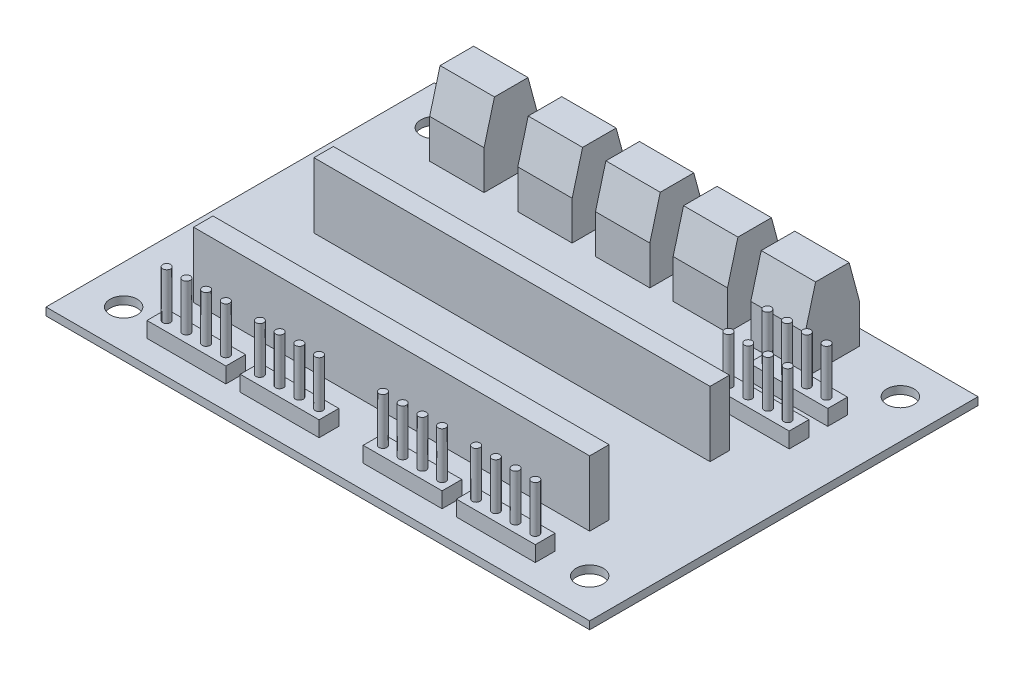
SolidWorks part; units mm, degrees
material "ABS"
ref_plane "Спереди" through (0, 0, 0) normal (0, 0, 1) x (1, 0, 0)
ref_plane "Сверху" through (0, 0, 0) normal (0, 1, 0) x (1, 0, 0)
ref_plane "Справа" through (0, 0, 0) normal (1, 0, 0) x (0, 0, -1)
sketch "Эскиз2" plane through (0, 0, 0) normal (0, 1, 0) x (1, 0, 0)
  line L0 (0, 25) -> (113.3637, 25) construction
  line L1 (0, 0) -> (70, 0)
  line L2 (0, 0) -> (0, 50)
  line L3 (0, 50) -> (70, 50)
  line L4 (70, 0) -> (70, 50)
  line L5 (35, 50) -> (35, -7.1391) construction
  circle A0 centre (5, 45) radius 1.75
  circle A1 centre (65, 45) radius 1.75
  circle A2 centre (65, 5) radius 1.75
  circle A3 centre (5, 5) radius 1.75
  dimension "D3" = 3.5
  dimension "D1" = 70
  dimension "D2" = 50
  dimension "D4" = 5
  dimension "D5" = 5
extrude "Бобышка-Вытянуть1" add sketch "Эскиз2" along normal blind 1
sketch "Эскиз3" plane through (0, 1, 0) normal (0, 1, 0) x (1, 0, 0)
  line L0 (0, 0) -> (70, 0) construction
  line L1 (9, 12.5) -> (60, 12.5)
  line L2 (9, 12.5) -> (9, 10)
  line L3 (9, 10) -> (60, 10)
  line L4 (60, 12.5) -> (60, 10)
  line L9 (70, 0) -> (70, 50) construction
  line L10 (60, 12.5) -> (60, 19) construction
  line L11 (60, 19) -> (7.0253, 19) construction
  line L12 (9, 28) -> (60, 28)
  line L13 (60, 25.5) -> (60, 28)
  line L14 (9, 25.5) -> (60, 25.5)
  line L15 (9, 25.5) -> (9, 28)
  dimension "D1" = 2.5
  dimension "D2" = 51
  dimension "D6" = 10
  dimension "D7" = 10
extrude "Бобышка-Вытянуть2" add sketch "Эскиз3" along normal blind 8.4
sketch "Эскиз4" plane through (0, 1, 0) normal (0, 1, 0) x (1, 0, 0)
  line L0 (70, 0) -> (70, 50) construction
  line L1 (60, 5.54) -> (49.84, 5.54)
  line L2 (60, 5.54) -> (60, 3)
  line L3 (60, 3) -> (49.84, 3)
  line L4 (49.84, 5.54) -> (49.84, 3)
  line L5 (0, 0) -> (70, 0) construction
  line L6 (48, 5.54) -> (48, 3)
  line L7 (35, 0) -> (35, 38.4524) construction
  line L8 (48, 5.54) -> (37.84, 5.54)
  line L9 (37.84, 5.54) -> (37.84, 3)
  line L10 (48, 3) -> (37.84, 3)
  line L11 (10, 3) -> (20.16, 3)
  line L12 (20.16, 5.54) -> (20.16, 3)
  line L13 (10, 5.54) -> (20.16, 5.54)
  line L14 (10, 5.54) -> (10, 3)
  line L15 (22, 5.54) -> (32.16, 5.54)
  line L16 (32.16, 5.54) -> (32.16, 3)
  line L17 (22, 3) -> (32.16, 3)
  line L18 (22, 5.54) -> (22, 3)
  line L19 (53.4823, 37.0132) -> (63.6423, 37.0132)
  line L20 (53.4823, 37.0132) -> (53.4823, 39.5532)
  line L21 (53.4823, 39.5532) -> (63.6423, 39.5532)
  line L22 (63.6423, 37.0132) -> (63.6423, 39.5532)
  line L23 (53.5146, 32.0132) -> (63.6746, 32.0132)
  line L24 (53.5146, 32.0132) -> (53.5146, 34.5532)
  line L25 (53.5146, 34.5532) -> (63.6746, 34.5532)
  line L26 (63.6746, 32.0132) -> (63.6746, 34.5532)
  dimension "D1" = 2.54
  dimension "D2" = 10.16
  dimension "D3" = 10
  dimension "D4" = 3
  dimension "D6" = 5
  dimension "D5" = 2
extrude "Бобышка-Вытянуть3" add sketch "Эскиз4" along normal blind 2
sketch "Эскиз5" plane through (0, 3, 0) normal (0, 1, 0) x (1, 0, 0)
  line L0 (60, 3) -> (60, 5.54) construction
  line L1 (49.84, 3) -> (60, 3) construction
  line L2 (35, 0) -> (35, 20.127) construction
  line L3 (0, 0) -> (70, 0) construction
  circle A0 centre (58.73, 4.27) radius 0.5
  circle A1 centre (56.19, 4.27) radius 0.5
  circle A2 centre (53.65, 4.27) radius 0.5
  circle A3 centre (51.11, 4.27) radius 0.5
  circle A4 centre (46.73, 4.27) radius 0.5
  circle A5 centre (44.19, 4.27) radius 0.5
  circle A6 centre (41.65, 4.27) radius 0.5
  circle A7 centre (39.11, 4.27) radius 0.5
  circle A8 centre (25.81, 4.27) radius 0.5
  circle A9 centre (11.27, 4.27) radius 0.5
  circle A10 centre (13.81, 4.27) radius 0.5
  circle A11 centre (16.35, 4.27) radius 0.5
  circle A12 centre (18.89, 4.27) radius 0.5
  circle A13 centre (23.27, 4.27) radius 0.5
  circle A14 centre (28.35, 4.27) radius 0.5
  circle A15 centre (30.89, 4.27) radius 0.5
  circle A16 centre (54.671, 33.2084) radius 0.5
  circle A17 centre (54.671, 38.2084) radius 0.5
  circle A20 centre (57.211, 33.2084) radius 0.5
  circle A21 centre (59.751, 33.2084) radius 0.5
  circle A22 centre (62.291, 33.2084) radius 0.5
  circle A23 centre (57.211, 38.2084) radius 0.5
  circle A24 centre (59.751, 38.2084) radius 0.5
  circle A25 centre (62.291, 38.2084) radius 0.5
  dimension "D1" = 1
  dimension "D2" = 1.27
  dimension "D3" = 1.27
  dimension "D4" = 4
  dimension "D5" = 2
  dimension "D6" = 4
  dimension "D7" = 2
extrude "Бобышка-Вытянуть4" add sketch "Эскиз5" along normal blind 6
sketch "Эскиз6" plane through (0, 1, 0) normal (0, 1, 0) x (1, 0, 0)
  line L0 (19.7472, 48.0002) -> (26.7472, 48.0002)
  line L5 (8.4463, 40.9536) -> (8.4463, 47.9536)
  line L6 (8.4463, 40.9536) -> (15.4463, 40.9536)
  line L7 (15.4463, 40.9536) -> (15.4463, 47.9536)
  line L8 (8.4463, 47.9536) -> (15.4463, 47.9536)
  line L9 (19.7472, 48.0002) -> (19.7472, 41.0002)
  line L10 (19.7472, 41.0002) -> (26.7472, 41.0002)
  line L11 (26.7472, 48.0002) -> (26.7472, 41.0002)
  line L12 (29.7472, 48.0002) -> (36.7472, 48.0002)
  line L13 (36.7472, 48.0002) -> (36.7472, 41.0002)
  line L14 (29.7472, 41.0002) -> (36.7472, 41.0002)
  line L15 (29.7472, 48.0002) -> (29.7472, 41.0002)
  line L16 (39.7472, 48.0002) -> (46.7472, 48.0002)
  line L17 (46.7472, 48.0002) -> (46.7472, 41.0002)
  line L18 (39.7472, 41.0002) -> (46.7472, 41.0002)
  line L19 (39.7472, 48.0002) -> (39.7472, 41.0002)
  line L20 (49.7472, 48.0002) -> (56.7472, 48.0002)
  line L21 (56.7472, 48.0002) -> (56.7472, 41.0002)
  line L22 (49.7472, 41.0002) -> (56.7472, 41.0002)
  line L23 (49.7472, 48.0002) -> (49.7472, 41.0002)
  dimension "D1" = 7
  dimension "D2" = 7
  dimension "D3" = 4
extrude "Бобышка-Вытянуть5" add sketch "Эскиз6" along normal blind 10
chamfer "Фаска1" distance 5 angle 15 10 edges at (53.2472, 11, -48.0002) (53.2472, 11, -41.0002) (43.2472, 11, -48.0002) (43.2472, 11, -41.0002) (33.2472, 11, -41.0002) (33.2472, 11, -48.0002) (23.2472, 11, -48.0002) (23.2472, 11, -41.0002) (11.9463, 11, -47.9536) (11.9463, 11, -40.9536) first distance on face at (53.2472, 6, -48.0002) first distance on face at (53.2472, 6, -41.0002) first distance on face at (43.2472, 6, -48.0002) first distance on face at (43.2472, 6, -41.0002) first distance on face at (33.2472, 6, -41.0002) first distance on face at (33.2472, 6, -48.0002) first distance on face at (23.2472, 6, -48.0002) first distance on face at (23.2472, 6, -41.0002) first distance on face at (11.9463, 6, -47.9536) first distance on face at (11.9463, 6, -40.9536)
